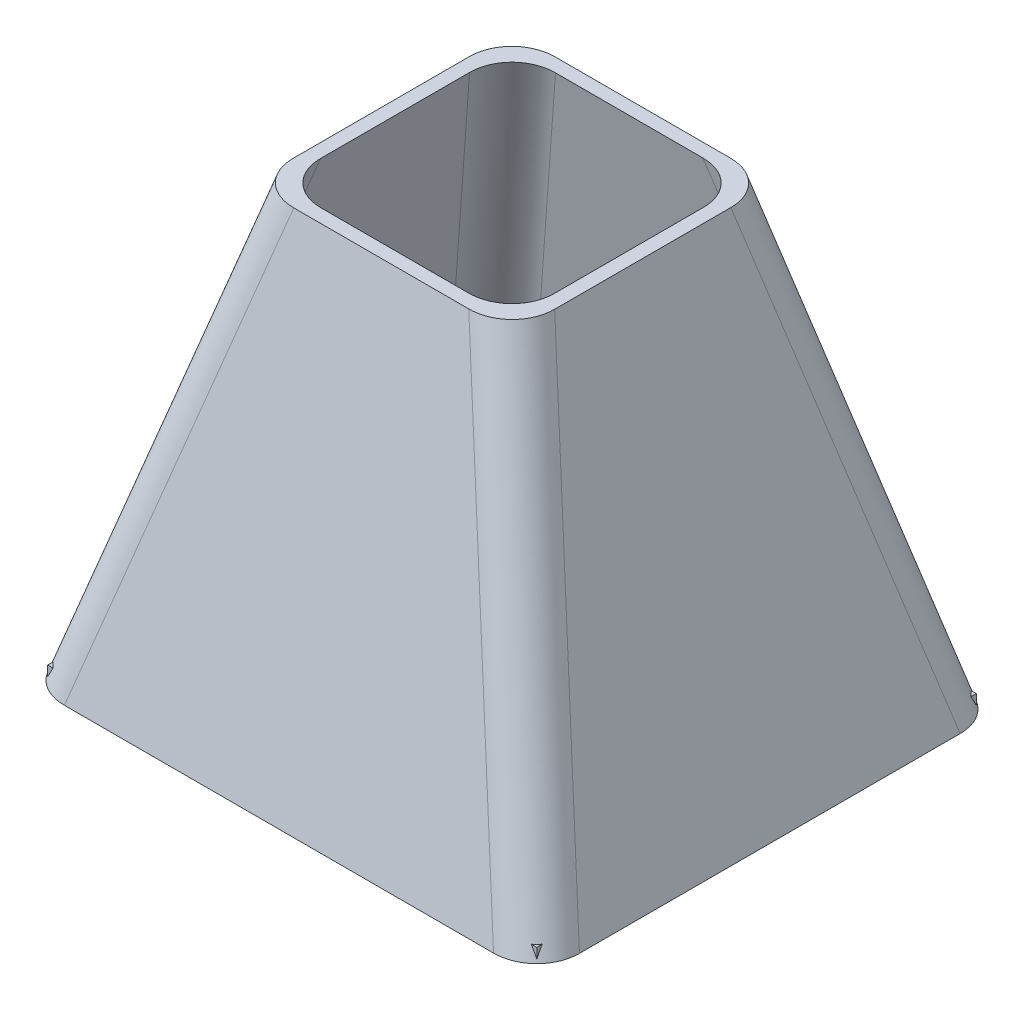
SolidWorks part; units mm, degrees
ref_plane "Front Plane" through (0, 0, 0) normal (0, 0, 1) x (1, 0, 0)
ref_plane "Top Plane" through (0, 0, 0) normal (0, 1, 0) x (1, 0, 0)
ref_plane "Right Plane" through (0, 0, 0) normal (1, 0, 0) x (0, 0, -1)
sketch "Sketch1" plane through (0, 0, 0) normal (0, 1, 0) x (1, 0, 0)
  line L1 (-29.5, -29.5) -> (29.5, -29.5)
  line L2 (-29.5, -29.5) -> (-29.5, 29.5)
  line L3 (-29.5, 29.5) -> (29.5, 29.5)
  line L4 (29.5, -29.5) -> (29.5, 29.5)
  line L5 (-29.5, -29.5) -> (29.5, 29.5) construction
  line L6 (-29.5, 29.5) -> (29.5, -29.5) construction
  point P0 (0, 0)
  dimension "D1" = 59
  dimension "D2" = 59
extrude "Boss-Extrude1" add sketch "Sketch1" against normal blind 100
ref_plane "Plane1" through (0, -100, 0) normal (0, 1, 0) x (1, 0, 0)
draft "Draft1" type of draft neutral plane draft angle 13 faces to draft 2 face at (0, -50, 29.5) face at (0, -50, -29.5) neutral plane through (0, 0, 0) neutral plane normal (0, 1, 0) parameters "D1"=13
draft "Draft2" type of draft neutral plane draft angle 16 faces to draft 2 face at (-29.5, -50, 0) face at (29.5, -50, 0) neutral plane through (0, 0, 0) neutral plane normal (0, 1, 0) parameters "D1"=16
shell "Shell1" thickness 3 removed face at (0, 0, 0)
sketch "Sketch3" plane through (0, -100, 0) normal (0, -1, 0) x (1, 0, 0)
  line L0 (-58.1745, 52.5868) -> (58.1745, 52.5868) construction
  line L1 (-55.1745, -49.5868) -> (55.1745, -49.5868)
  line L2 (-55.1745, -49.5868) -> (-55.1745, 49.5868)
  line L3 (-55.1745, 49.5868) -> (55.1745, 49.5868)
  line L4 (55.1745, -49.5868) -> (55.1745, 49.5868)
  line L5 (-55.1745, -49.5868) -> (55.1745, 49.5868) construction
  line L6 (-55.1745, 49.5868) -> (55.1745, -49.5868) construction
  line L7 (58.1745, 52.5868) -> (58.1745, -52.5868) construction
  point P0 (0, 0)
  dimension "D1" = 3
  dimension "D2" = 3
extrude "Cut-Extrude2" cut sketch "Sketch3" against normal blind 3
fillet "Fillet1" radius 10 8 edges at (-40.2863, -48.5, 37.6182) (40.2863, -48.5, 37.6182) (40.2863, -48.5, -37.6182) (-40.2863, -48.5, -37.6182) (43.8373, -50, 41.0434) (-43.8373, -50, 41.0434) (-43.8373, -50, -41.0434) (43.8373, -50, -41.0434)
